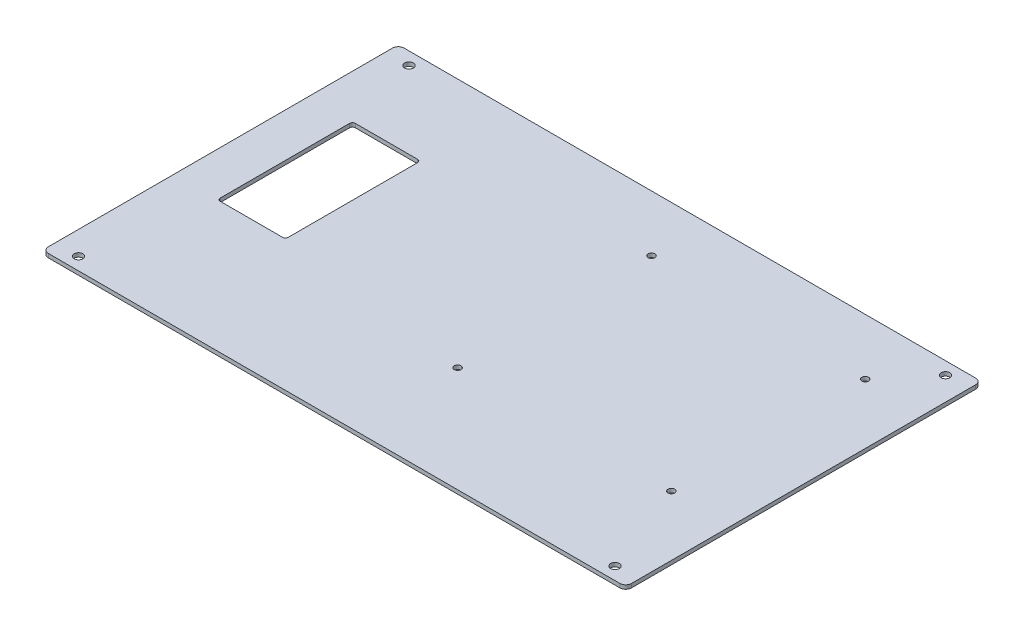
SolidWorks part; units mm, degrees
ref_plane "Front Plane" through (0, 0, 0) normal (0, 0, 1) x (1, 0, 0)
ref_plane "Top Plane" through (0, 0, 0) normal (0, 1, 0) x (1, 0, 0)
ref_plane "Right Plane" through (0, 0, 0) normal (1, 0, 0) x (0, 0, -1)
sketch "Sketch1" plane through (0, 0, 0) normal (0, 1, 0) x (1, 0, 0)
  line L0 (164.6344, -145.7557) -> (-129.3656, -145.7557)
  line L1 (167.6344, -142.7557) -> (167.6344, 34.2443)
  line L2 (164.6344, 37.2443) -> (-129.3656, 37.2443)
  line L3 (-132.3656, -142.7557) -> (-132.3656, 34.2443)
  arc A0 (167.6344, 34.2443) -> (164.6344, 37.2443) centre (164.6344, 34.2443) ccw
  arc A1 (164.6344, -145.7557) -> (167.6344, -142.7557) centre (164.6344, -142.7557) ccw
  arc A2 (-129.3656, -145.7557) -> (-132.3656, -142.7557) centre (-129.3656, -142.7557) cw
  arc A3 (-132.3656, 34.2443) -> (-129.3656, 37.2443) centre (-129.3656, 34.2443) cw
  dimension "D1" = 3
  dimension "D2" = 183
base flange "Base-Flange2" sketch "Sketch1" thickness 2 reverse thickness direction no parameters "D1"=0.5
sketch "Sketch2" plane through (0, 0, 0) normal (0, 1, 0) x (1, 0, 0)
  circle A2 centre (-120.3656, 30.7443) radius 2.25
  circle A3 centre (-120.3656, -139.2557) radius 2.25
  circle A6 centre (155.6344, -139.2557) radius 2.25
  circle A7 centre (155.6344, 30.7443) radius 2.25
  dimension "D4" = 4.5
extrude "Cut-Extrude4" cut sketch "Sketch2" against normal blind 10 normal cut yes
sketch "Sketch3" plane through (0, 0, 0) normal (0, 1, 0) x (1, 0, 0)
  line L23 (-107.8362, -8.8349) -> (-76.3683, -8.8349)
  line L25 (-74.8683, -10.3349) -> (-74.8683, -76.8227)
  line L26 (-107.8362, -8.8349) -> (-108.3629, -8.8349)
  line L27 (-76.8951, -78.3227) -> (-107.8362, -78.3227)
  line L28 (-109.8629, -76.8227) -> (-109.8629, -10.3349)
  line L29 (-76.8951, -78.3227) -> (-76.3683, -78.3227)
  line L30 (-108.3629, -78.3227) -> (-107.8362, -78.3227)
  arc A8 (-74.8683, -10.3349) -> (-76.3683, -8.8349) centre (-76.3683, -10.3349) ccw
  arc A9 (-109.8629, -76.8227) -> (-108.3629, -78.3227) centre (-108.3629, -76.8227) ccw
  arc A10 (-108.3629, -8.8349) -> (-109.8629, -10.3349) centre (-108.3629, -10.3349) ccw
  arc A11 (-76.3683, -78.3227) -> (-74.8683, -76.8227) centre (-76.3683, -76.8227) ccw
extrude "Cut-Extrude3" cut sketch "Sketch3" against normal blind 10 normal cut yes
sketch "Sketch6" plane through (0, 0, 0) normal (0, 1, 0) x (1, 0, 0)
  spline S4 degree 3 poles (28.4314, -92.0682) (28.5671, -91.386) (28.4314, -90.7038) (28.045, -90.1255) (27.4666, -89.739) (26.7844, -89.6033) (26.1022, -89.739) (25.5239, -90.1255) (25.1374, -90.7038) (25.0017, -91.386) (25.1374, -92.0682) (25.5239, -92.6466) (26.1022, -93.033) (26.7844, -93.1687) (27.4666, -93.033) (28.045, -92.6466) (28.4314, -92.0682) (28.5671, -91.386) (28.4314, -90.7038) knots -0.1875 -0.125 -0.0625 0 0.0625 0.125 0.1875 0.25 0.3125 0.375 0.4375 0.5 0.5625 0.625 0.6875 0.75 0.8125 0.875 0.9375 1 1.0625 1.125 1.1875 only from (28.5219, -91.386) to (28.5219, -91.386)
  spline S5 degree 3 poles (138.3814, 7.6818) (138.5171, 8.364) (138.3814, 9.0462) (137.995, 9.6245) (137.4166, 10.011) (136.7344, 10.1467) (136.0522, 10.011) (135.4739, 9.6245) (135.0874, 9.0462) (134.9517, 8.364) (135.0874, 7.6818) (135.4739, 7.1034) (136.0522, 6.717) (136.7344, 6.5813) (137.4166, 6.717) (137.995, 7.1034) (138.3814, 7.6818) (138.5171, 8.364) (138.3814, 9.0462) knots -0.1875 -0.125 -0.0625 0 0.0625 0.125 0.1875 0.25 0.3125 0.375 0.4375 0.5 0.5625 0.625 0.6875 0.75 0.8125 0.875 0.9375 1 1.0625 1.125 1.1875 only from (138.4719, 8.364) to (138.4719, 8.364)
  spline S6 degree 3 poles (28.4314, 7.6818) (28.5671, 8.364) (28.4314, 9.0462) (28.045, 9.6245) (27.4666, 10.011) (26.7844, 10.1467) (26.1022, 10.011) (25.5239, 9.6245) (25.1374, 9.0462) (25.0017, 8.364) (25.1374, 7.6818) (25.5239, 7.1034) (26.1022, 6.717) (26.7844, 6.5813) (27.4666, 6.717) (28.045, 7.1034) (28.4314, 7.6818) (28.5671, 8.364) (28.4314, 9.0462) knots -0.1875 -0.125 -0.0625 0 0.0625 0.125 0.1875 0.25 0.3125 0.375 0.4375 0.5 0.5625 0.625 0.6875 0.75 0.8125 0.875 0.9375 1 1.0625 1.125 1.1875 only from (28.5219, 8.364) to (28.5219, 8.364)
  spline S7 degree 3 poles (138.3814, -92.0682) (138.5171, -91.386) (138.3814, -90.7038) (137.995, -90.1255) (137.4166, -89.739) (136.7344, -89.6033) (136.0522, -89.739) (135.4739, -90.1255) (135.0874, -90.7038) (134.9517, -91.386) (135.0874, -92.0682) (135.4739, -92.6466) (136.0522, -93.033) (136.7344, -93.1687) (137.4166, -93.033) (137.995, -92.6466) (138.3814, -92.0682) (138.5171, -91.386) (138.3814, -90.7038) knots -0.1875 -0.125 -0.0625 0 0.0625 0.125 0.1875 0.25 0.3125 0.375 0.4375 0.5 0.5625 0.625 0.6875 0.75 0.8125 0.875 0.9375 1 1.0625 1.125 1.1875 only from (138.4719, -91.386) to (138.4719, -91.386)
extrude "Cut-Extrude5" cut sketch "Sketch6" against normal blind 10 normal cut yes
sketch "Bend-Lines3" [suppressed] plane through (0, 0, 0) normal (0, 1, 0) x (1, 0, 0)
sketch "Bounding-Box3" [suppressed] plane through (0, 0, 0) normal (0, 1, 0) x (1, 0, 0)
sheet metal parameters "Sheet-Metal2" thickness 2 parameters "D1"=0.5
flat pattern "Flat-Pattern2" [suppressed]
sketch "Bend-Lines4" plane through (0, 0, 0) normal (0, 1, 0) x (1, 0, 0)
sketch3d "Bounding-Box4" [suppressed]
  line L0 (-297, -172.1769, 0) -> (3, -172.1769, 0) construction
  line L1 (-297, 3, 0) -> (3, 3, 0) construction
  line L2 (-297, -172.1769, 0) -> (-297, 3, 0) construction
  line L3 (3, -172.1769, 0) -> (3, 3, 0) construction
sheet metal parameters "Sheet-Metal5" thickness 2 parameters "D1"=0.5
flat pattern "Flat-Pattern2"
sketch "Bend-Lines4" plane through (0, 0, 0) normal (0, 1, 0) x (1, 0, 0)
sketch3d "Bounding-Box4" [suppressed]
  line L0 (-297, -180, 0) -> (3, -180, 0) construction
  line L1 (-297, 3, 0) -> (3, 3, 0) construction
  line L2 (-297, -180, 0) -> (-297, 3, 0) construction
  line L3 (3, -180, 0) -> (3, 3, 0) construction
sheet metal parameters "Sheet-Metal6" thickness 2 parameters "D1"=0.5
flat pattern "Flat-Pattern2"
sketch "Bend-Lines4" plane through (0, 0, 0) normal (0, 1, 0) x (1, 0, 0)
sketch3d "Bounding-Box4" [suppressed]
  line L0 (-297, -172.1769, 0) -> (3, -172.1769, 0) construction
  line L1 (-297, 3, 0) -> (3, 3, 0) construction
  line L2 (-297, -172.1769, 0) -> (-297, 3, 0) construction
  line L3 (3, -172.1769, 0) -> (3, 3, 0) construction
sheet metal parameters "Sheet-Metal7" thickness 2 parameters "D1"=0.5
flat pattern "Flat-Pattern2"
sketch "Bend-Lines4" plane through (0, 0, 0) normal (0, 1, 0) x (1, 0, 0)
sketch3d "Bounding-Box4" [suppressed]
  line L0 (-297, -180, 0) -> (3, -180, 0) construction
  line L1 (-297, 3, 0) -> (3, 3, 0) construction
  line L2 (-297, -180, 0) -> (-297, 3, 0) construction
  line L3 (3, -180, 0) -> (3, 3, 0) construction
